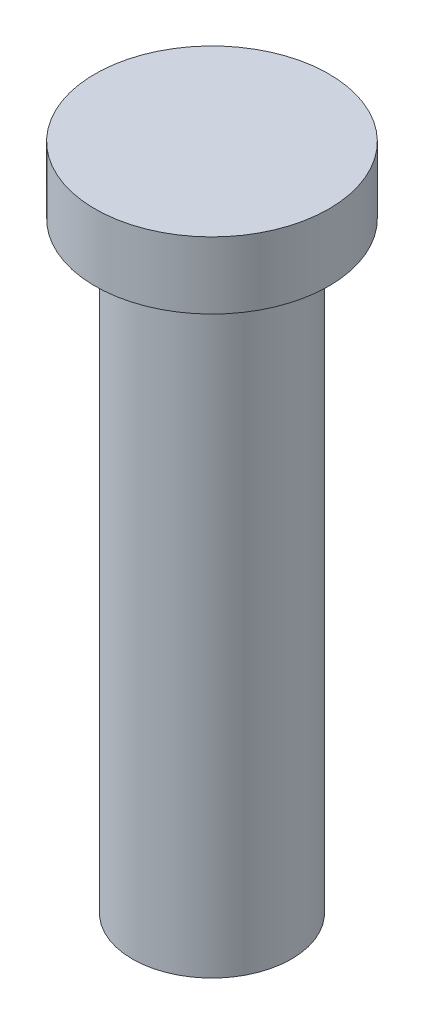
SolidWorks part; units mm, degrees
material "Plain Carbon Steel"
ref_plane "Front Plane" through (0, 0, 0) normal (0, 0, 1) x (1, 0, 0)
ref_plane "Top Plane" through (0, 0, 0) normal (0, 1, 0) x (1, 0, 0)
ref_plane "Right Plane" through (0, 0, 0) normal (1, 0, 0) x (0, 0, -1)
sketch "Sketch1" plane through (0, 0, 0) normal (0, 0, 1) x (1, 0, 0)
  line L0 (0, 0) -> (0, 40) construction
  line L1 (0, 0) -> (4.7625, 0)
  line L2 (4.7625, 0) -> (4.7625, 36)
  line L3 (4.7625, 36) -> (7, 36)
  line L4 (7, 36) -> (7, 40)
  line L5 (7, 40) -> (0, 40)
  line L6 (0, 40) -> (0, 0)
  dimension "D1" = 4.7625
  dimension "D2" = 36
  dimension "D3" = 2.2375
  dimension "D4" = 4
revolve "Revolve1" add sketch "Sketch1" angle 360 about L0
